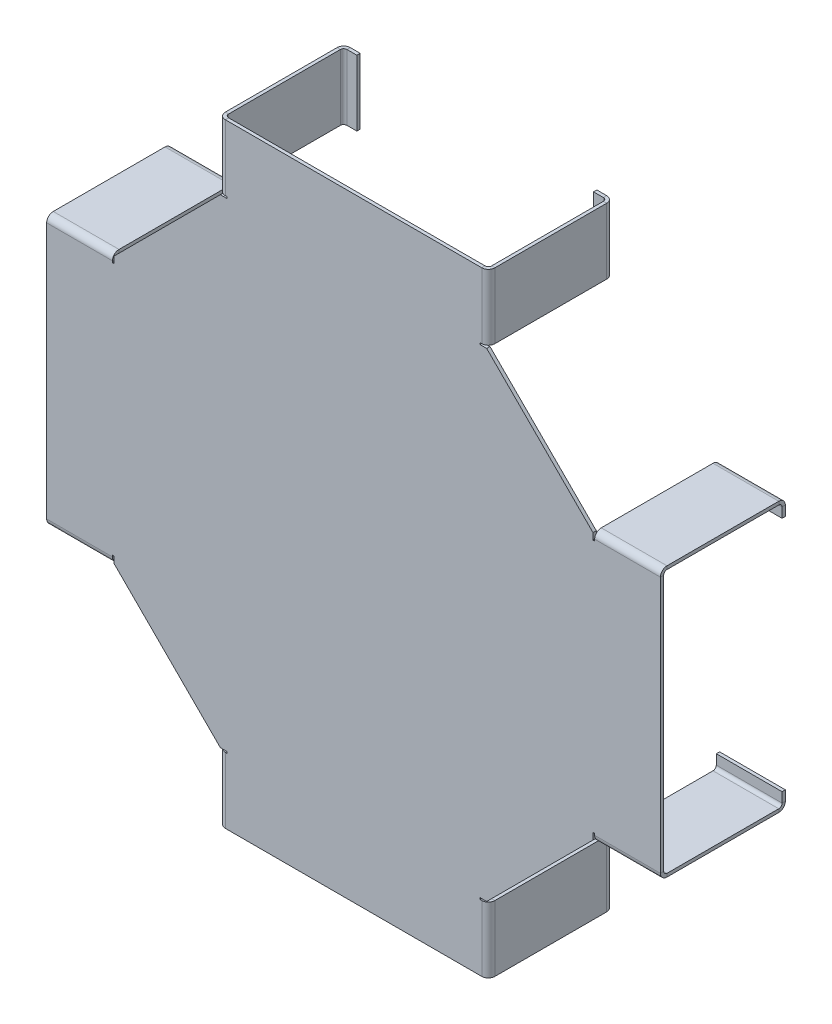
SolidWorks part; units mm, degrees
note: The reader was unsure of these and kept them because the rebuilt part matched: flange length of "Ребро-кромка1", "Ребро-кромка2".
material "AISI 1020"
ref_plane "Спереди" through (0, 0, 0) normal (0, 0, 1) x (1, 0, 0)
ref_plane "Сверху" through (0, 0, 0) normal (0, 1, 0) x (1, 0, 0)
ref_plane "Справа" through (0, 0, 0) normal (1, 0, 0) x (0, 0, -1)
sketch "Эскиз1" plane through (0, 0, 0) normal (0, 0, 1) x (1, 0, 0)
  line L0 (0, -1000) -> (0, 49000) construction
  line L1 (-1000, 0) -> (49000, 0) construction
  line L2 (-70, 0) -> (-70, 30)
  line L3 (-70, 30) -> (-55, 30)
  line L4 (-55, 30) -> (-42.5, 42.5)
  line L7 (0, 0) -> (-42.5, 42.5)
  line L8 (-70, 0) -> (0, 0)
  dimension "D1" = 45
  dimension "D2" = 60
  dimension "D3" = 15
  dimension "D4" = 12.5
base flange "Базовая кромка1" sketch "Эскиз1" thickness 0.75 reverse thickness direction no parameters "D1"=0.75
edge flange "Ребро-кромка1" sketch "Эскиз8" flange angle 90 flange length 27 flange position material outside bend radius 0.75 thickness 0.75 parameters "D6"=10
sketch "Эскиз8" plane through (0, 30, -0.75) normal (0, 1, 0) x (1, 0, 0)
  line L0 (-55, 0) -> (-70, 0) construction
  line L1 (-55, 0) -> (-70, 0)
  line L2 (-70, 0) -> (-70, 27)
  line L3 (-70, 27) -> (-55, 27)
  line L4 (-55, 27) -> (-55, 0)
bend "EdgeBend1" bend radius 0.75 bend angle 90 parameters "D5"=1
edge flange "Ребро-кромка2" sketch "Эскиз11" flange angle 90 flange length 3 flange position material outside bend radius 0.75 thickness 0.75 parameters "D6"=10
sketch "Эскиз11" plane through (0, 30, -27.75) normal (0, 0, -1) x (1, 0, 0)
  line L0 (-55, 0) -> (-70, 0) construction
  line L1 (-55, 0) -> (-70, 0)
  line L2 (-70, 0) -> (-70, 3)
  line L3 (-70, 3) -> (-55, 3)
  line L4 (-55, 3) -> (-55, 0)
bend "EdgeBend2" bend radius 0.75 bend angle 90 parameters "D5"=2
mirror "Зеркальное отражение1" about plane through (-70, 0, -0.75) normal (0, -1, 0) of bodies 105
bend "Зеркальное отражение сгиба1" bend radius 0.75 bend angle 90 parameters "D5"=3
bend "Зеркальное отражение сгиба2" bend radius 0.75 bend angle 90 parameters "D5"=4
mirror "Зеркальное отражение2" about plane through (0, 0, -0.75) normal (0.7071, -0.7071, 0) of bodies 106
bend "Зеркальное отражение сгиба3" bend radius 0.75 bend angle 90 parameters "D5"=5
bend "Зеркальное отражение сгиба4" bend radius 0.75 bend angle 90 parameters "D5"=6
bend "Зеркальное отражение сгиба5" bend radius 0.75 bend angle 90 parameters "D5"=7
bend "Зеркальное отражение сгиба6" bend radius 0.75 bend angle 90 parameters "D5"=8
mirror "Зеркальное отражение3"
bend "Зеркальное отражение сгиба7" bend radius 0.75 bend angle 90 parameters "D5"=9
bend "Зеркальное отражение сгиба8" bend radius 0.75 bend angle 90 parameters "D5"=10
bend "Зеркальное отражение сгиба9" bend radius 0.75 bend angle 90 parameters "D5"=11
bend "Зеркальное отражение сгиба10" bend radius 0.75 bend angle 90 parameters "D5"=12
bend "Зеркальное отражение сгиба11" bend radius 0.75 bend angle 90 parameters "D5"=13
bend "Зеркальное отражение сгиба12" bend radius 0.75 bend angle 90 parameters "D5"=14
bend "Зеркальное отражение сгиба13" bend radius 0.75 bend angle 90 parameters "D5"=15
bend "Зеркальное отражение сгиба14" bend radius 0.75 bend angle 90 parameters "D5"=16
sketch "Сгиб-Линии1" plane through (0, 0, 0) normal (0, 1, 0) x (1, 0, 0)
sketch "Граничная рамка1" plane through (0, 0, 0) normal (0, 1, 0) x (1, 0, 0)
sheet metal parameters "Листовой металл3" thickness 0.75 parameters "D1"=0.75
flat pattern "Развертка3" [suppressed]
sketch "Сгиб-Линии2" plane through (0, 0, 0) normal (0, 1, 0) x (1, 0, 0)
sketch "Граничная рамка2" [suppressed] plane through (0, 0, 0) normal (0, 1, 0) x (1, 0, 0)
sheet metal parameters "Листовой металл4" thickness 0.75 parameters "D1"=0.75
flat pattern "Развертка3" [suppressed]
sketch "Сгиб-Линии2" plane through (0, 0, 0) normal (0, 1, 0) x (1, 0, 0)
sketch "Граничная рамка2" [suppressed] plane through (0, 0, 0) normal (0, 1, 0) x (1, 0, 0)
bend of the flat pattern "Плоское состояние-<EdgeBend1>1"
sheet metal parameters "Листовой металл5" thickness 0.75 parameters "D1"=0.75
flat pattern "Развертка3" [suppressed]
sketch "Сгиб-Линии2" plane through (0, 0, 0) normal (0, 1, 0) x (1, 0, 0)
sketch "Граничная рамка2" [suppressed] plane through (0, 0, 0) normal (0, 1, 0) x (1, 0, 0)
bend of the flat pattern "Плоское состояние-<EdgeBend1>1"
bend of the flat pattern "Плоское состояние-<EdgeBend2>1"
sheet metal parameters "Листовой металл6" thickness 0.75 parameters "D1"=0.75
flat pattern "Развертка6" [suppressed]
sketch "Сгиб-Линии3" plane through (0, 0, 0) normal (0, 1, 0) x (1, 0, 0)
sketch "Граничная рамка3" [suppressed] plane through (0, 0, 0) normal (0, 1, 0) x (1, 0, 0)
bend of the flat pattern "Плоское состояние-<EdgeBend1>2"
bend of the flat pattern "Плоское состояние-<EdgeBend2>2"
bend of the flat pattern "Плоское состояние-<Зеркальное отражение сгиба1>1"
bend of the flat pattern "Плоское состояние-<Зеркальное отражение сгиба2>1"
sheet metal parameters "Листовой металл7" thickness 0.75 parameters "D1"=0.75
flat pattern "Развертка7" [suppressed]
sketch "Сгиб-Линии4" plane through (0, 0, 0) normal (0, 1, 0) x (1, 0, 0)
sketch "Граничная рамка4" [suppressed] plane through (0, 0, 0) normal (0, 1, 0) x (1, 0, 0)
bend of the flat pattern "Плоское состояние-<EdgeBend1>3"
bend of the flat pattern "Плоское состояние-<EdgeBend2>3"
bend of the flat pattern "Плоское состояние-<Зеркальное отражение сгиба1>2"
bend of the flat pattern "Плоское состояние-<Зеркальное отражение сгиба2>2"
bend of the flat pattern "Плоское состояние-<Зеркальное отражение сгиба3>1"
bend of the flat pattern "Плоское состояние-<Зеркальное отражение сгиба4>1"
bend of the flat pattern "Плоское состояние-<Зеркальное отражение сгиба5>1"
bend of the flat pattern "Плоское состояние-<Зеркальное отражение сгиба6>1"
sheet metal parameters "Листовой металл8" thickness 0.75 parameters "D1"=0.75
flat pattern "Развертка8" [suppressed]
sketch "Сгиб-Линии5" plane through (0, 0, 0) normal (0, 1, 0) x (1, 0, 0)
sketch "Граничная рамка5" [suppressed] plane through (0, 0, 0) normal (0, 1, 0) x (1, 0, 0)
bend of the flat pattern "Плоское состояние-<EdgeBend1>4"
bend of the flat pattern "Плоское состояние-<EdgeBend2>4"
bend of the flat pattern "Плоское состояние-<Зеркальное отражение сгиба1>3"
bend of the flat pattern "Плоское состояние-<Зеркальное отражение сгиба2>3"
bend of the flat pattern "Плоское состояние-<Зеркальное отражение сгиба3>2"
bend of the flat pattern "Плоское состояние-<Зеркальное отражение сгиба4>2"
bend of the flat pattern "Плоское состояние-<Зеркальное отражение сгиба5>2"
bend of the flat pattern "Плоское состояние-<Зеркальное отражение сгиба6>2"
bend of the flat pattern "Плоское состояние-<Зеркальное отражение сгиба7>1"
bend of the flat pattern "Плоское состояние-<Зеркальное отражение сгиба8>1"
bend of the flat pattern "Плоское состояние-<Зеркальное отражение сгиба9>1"
bend of the flat pattern "Плоское состояние-<Зеркальное отражение сгиба10>1"
bend of the flat pattern "Плоское состояние-<Зеркальное отражение сгиба11>1"
bend of the flat pattern "Плоское состояние-<Зеркальное отражение сгиба12>1"
bend of the flat pattern "Плоское состояние-<Зеркальное отражение сгиба13>1"
bend of the flat pattern "Плоское состояние-<Зеркальное отражение сгиба14>1"
